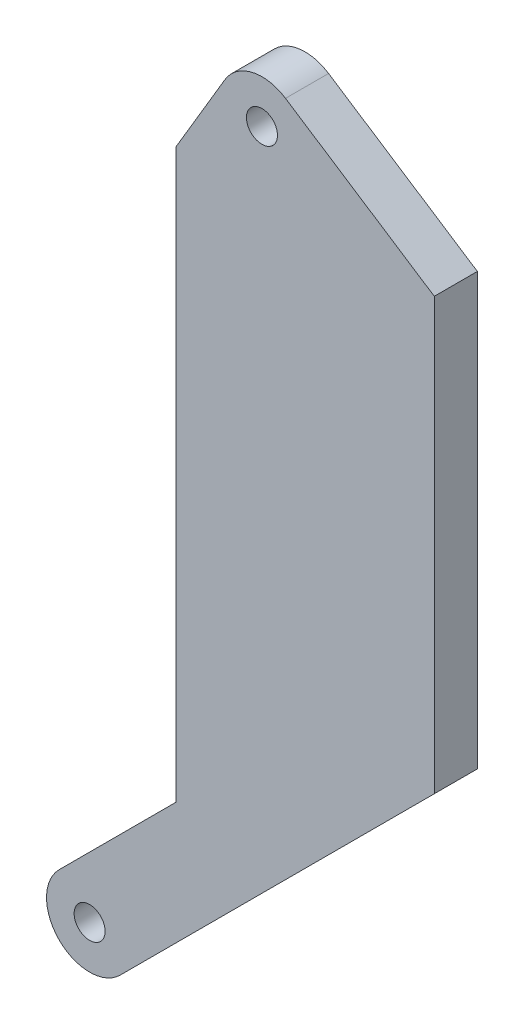
SolidWorks part; units mm, degrees
ref_plane "Front Plane" through (0, 0, 0) normal (0, 0, 1) x (1, 0, 0)
ref_plane "Top Plane" through (0, 0, 0) normal (0, 1, 0) x (1, 0, 0)
ref_plane "Right Plane" through (0, 0, 0) normal (1, 0, 0) x (0, 0, -1)
sketch "Sketch1" plane through (0, 0, 0) normal (0, 0, 1) x (1, 0, 0)
  line L0 (-4.4901, 4.4901) -> (12.7, 21.6803)
  line L1 (12.7, 21.6803) -> (12.7, 105.3197)
  line L2 (4.4901, -4.4901) -> (50.8, 41.8197)
  line L3 (50.8, 41.8197) -> (50.8, 105.3197)
  line L4 (50.8, 105.3197) -> (28.8681, 119.6193)
  line L5 (19.9366, 117.5363) -> (12.7, 105.3197)
  line L6 (0, 0) -> (50.8, 0) construction
  circle A0 centre (0, 0) radius 2.286
  arc A1 (-4.4901, 4.4901) -> (4.4901, -4.4901) centre (0, 0) ccw
  arc A2 (28.8681, 119.6193) -> (19.9366, 117.5363) centre (25.4, 114.3) ccw
  circle A3 centre (25.4, 114.3) radius 2.286
  point P14 (46.3099, 199.8809)
  point P16 (50.8, 95.4649)
  point P17 (31.75, 115.364)
  point P18 (50.8, 136.2183)
  point P19 (50.8, 98.9672)
  point P20 (30.5453, 113.9313)
  point P21 (0, 0)
  dimension "D1" = 12.7
  dimension "D2" = 4.572
  dimension "D8" = 63.5
  dimension "D3" = 38.1
  dimension "D4" = 25.4
  dimension "D5" = 12.7
  dimension "D6" = 45
  dimension "D7" = 114.3
extrude "Boss-Extrude1" add sketch "Sketch1" along normal blind 6.35
